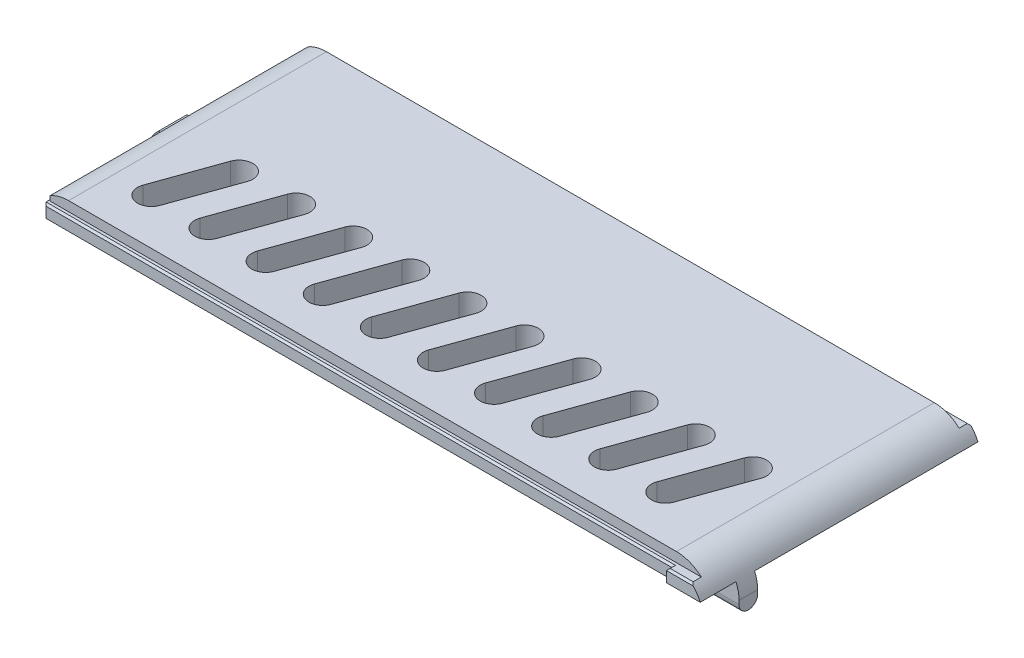
SolidWorks part; units mm, degrees
ref_plane "前视基准面" through (0, 0, 0) normal (0, 0, 1) x (1, 0, 0)
ref_plane "上视基准面" through (0, 0, 0) normal (0, 1, 0) x (1, 0, 0)
ref_plane "右视基准面" through (0, 0, 0) normal (1, 0, 0) x (0, 0, -1)
sketch "草图2" plane through (0, 0, 0) normal (0, 1, 0) x (1, 0, 0)
  line L1 (-31.0872, 15.1404) -> (42.9128, 15.1404)
  line L2 (-31.0872, 15.1404) -> (-31.0872, -12.8596)
  line L3 (-31.0872, -12.8596) -> (42.9128, -12.8596)
  line L4 (42.9128, 15.1404) -> (42.9128, -12.8596)
  dimension "D1" = 74
  dimension "D2" = 28
extrude "凸台-拉伸1" add sketch "草图2" along normal blind 4
fillet "圆角1" radius 4 2 edges at (-31.0872, 4, -1.1404) (42.9128, 4, -1.1404)
sketch "草图3" plane through (0, 0, -15.1404) normal (0, 0, -1) x (-1, 0, 0)
  line L1 (31.0872, 0) -> (-42.9128, 0)
  line L2 (31.0872, 0) -> (31.0872, 1.6)
  line L3 (31.0872, 1.6) -> (-42.9128, 1.6)
  line L4 (-42.9128, 0) -> (-42.9128, 1.6)
  point P4 (0, 0)
  point P5 (0, 0)
  point P6 (0, 0)
  point P9 (31.0872, 0)
  dimension "D1" = 1.6
extrude "切除-拉伸1" cut sketch "草图3" against normal through all
sketch "草图15" plane through (0, 1.6, 0) normal (0, -1, 0) x (1, 0, 0)
  line L1 (45.2778, 8.0374) -> (33.5789, 8.0374)
  line L2 (45.2778, 8.0374) -> (45.2778, 10.0596)
  line L3 (45.2778, 10.0596) -> (33.5789, 10.0596)
  line L4 (33.5789, 8.0374) -> (33.5789, 10.0596)
  line L5 (42.5789, -15.1404) -> (42.5789, 12.8596) construction
  dimension "D1" = 2.0222
  dimension "D2" = 9
extrude "凸台-拉伸8" add sketch "草图15" along normal blind 3
sketch "草图17" plane through (0, 0, 10.0596) normal (0, 0, 1) x (1, 0, 0)
  line L0 (42.9128, 0) -> (42.9128, -28) construction
  line L1 (42.9128, 0) -> (42.9128, -1.4)
  line L2 (45.2778, -1.4) -> (33.5789, -1.4) construction
  line L3 (42.9128, -1.4) -> (46.903, -1.4)
  line L4 (46.903, -1.4) -> (46.903, 1.6)
  line L5 (46.903, 1.6) -> (42.5789, 1.6)
  arc A0 (42.5789, 1.6) -> (42.9128, 0) centre (38.9128, 0) cw
extrude "切除-拉伸5" cut sketch "草图17" against normal through all
chamfer "倒角3" distance 3.5 angle 19 1 edges at (33.5789, 0.1, 10.0596) first distance on face at (39.129, 0.0834, 10.0596)
sketch "草图4" plane through (0, 0, 12.8596) normal (0, 0, 1) x (1, 0, 0)
  line L0 (-31.0872, 0) -> (-31.0872, -28) construction
  line L1 (-31.0872, -1.1213) -> (-29.0872, -1.1213)
  line L2 (-31.0872, -1.1213) -> (-31.0872, 6.7558)
  line L3 (-31.0872, 6.7558) -> (-29.0872, 6.7558)
  line L4 (-29.0872, -1.1213) -> (-29.0872, 6.7558)
  dimension "D1" = 2
extrude "切除-拉伸2" cut sketch "草图4" against normal through all
sketch "草图5" plane through (0, 0, 12.8596) normal (0, 0, 1) x (1, 0, 0)
  line L0 (-29.0872, 1.6) -> (42.5789, 1.6) construction
  line L1 (38.9128, 1.6) -> (-29.0872, 1.6)
  line L2 (38.9128, 1.6) -> (38.9128, 2.95)
  line L3 (38.9128, 2.95) -> (-29.0872, 2.95)
  line L4 (-29.0872, 1.6) -> (-29.0872, 2.95)
  line L6 (-29.0872, 1.6) -> (-29.0872, 3.4641) construction
  dimension "D1" = 1.35
extrude "凸台-拉伸2" add sketch "草图5" along normal blind 0.5
sketch "草图6" plane through (0, 0, -15.1404) normal (0, 0, -1) x (-1, 0, 0)
  line L4 (-38.9128, 2.95) -> (-38.9128, 1.6)
  line L5 (29.0872, 2.95) -> (-38.9128, 2.95)
  line L6 (29.0872, 1.6) -> (29.0872, 2.95)
  line L7 (-38.9128, 1.6) -> (29.0872, 1.6)
  line L8 (-38.9128, 2.95) -> (-38.9128, 1.6)
  line L9 (29.0872, 2.95) -> (-38.9128, 2.95)
  line L10 (29.0872, 1.6) -> (29.0872, 2.95)
  line L11 (-38.9128, 1.6) -> (29.0872, 1.6)
  dimension "D1" = 0
extrude "凸台-拉伸3" add sketch "草图6" along normal blind 0.5
sketch "草图7" plane through (-29.0872, 0, 0) normal (-1, 0, 0) x (0, 0, 1)
  line L1 (13.3596, 2.95) -> (-15.6404, 2.95)
  line L2 (13.3596, 2.95) -> (13.3596, 1.6)
  line L3 (13.3596, 1.6) -> (-15.6404, 1.6)
  line L4 (-15.6404, 2.95) -> (-15.6404, 1.6)
extrude "凸台-拉伸4" add sketch "草图7" along normal blind 0.15
sketch "草图10" plane through (0, 0, -15.1404) normal (0, 0, -1) x (-1, 0, 0)
  line L0 (-38.9128, 2.95) -> (-42.3685, 2.95) construction
  line L1 (-42.5789, 1.6) -> (-38.9128, 1.6)
  line L2 (-38.9128, 1.6) -> (-38.9128, 2.95)
  line L3 (-38.9128, 2.95) -> (-41.6142, 2.95)
  arc A0 (-42.5789, 1.6) -> (-41.6142, 2.95) centre (-38.9128, 0) cw
extrude "凸台-拉伸5" add sketch "草图10" along normal blind 1.08
sketch "草图11" plane through (0, 0, 12.8596) normal (0, 0, 1) x (1, 0, 0)
  line L3 (38.9128, 1.6) -> (42.5789, 1.6)
  line L4 (38.9128, 2.95) -> (38.9128, 1.6)
  line L5 (41.6142, 2.95) -> (38.9128, 2.95)
  line L6 (38.9128, 1.6) -> (42.5789, 1.6)
  line L7 (38.9128, 2.95) -> (38.9128, 1.6)
  line L8 (41.6142, 2.95) -> (38.9128, 2.95)
  arc A1 (42.5789, 1.6) -> (41.6142, 2.95) centre (38.9128, 0) ccw
  arc A2 (42.5789, 1.6) -> (41.6142, 2.95) centre (38.9128, 0) ccw
  dimension "D1" = 0
extrude "凸台-拉伸6" add sketch "草图11" along normal blind 1.08
chamfer "倒角1" distance 0.2 angle 45 9 edges at (40.2635, 2.95, -16.2204) (40.2635, 2.95, 13.9396) (4.8378, 2.95, -15.6404) (-29.2372, 2.275, -15.6404) (-29.2372, 1.6, -1.1404) (-29.2372, 2.275, 13.3596) (4.8378, 2.95, 13.3596) (38.9128, 2.95, -15.9304) (38.9128, 2.95, 13.6496)
sketch "草图12" plane through (-29.2372, 0, 0) normal (-1, 0, 0) x (0, 0, 1)
  line L0 (-1.1404, 1.8) -> (-1.1404, 4.7248) construction
  line L2 (-15.4404, 1.8) -> (13.1596, 1.8) construction
  line L3 (14.3032, 2.375) -> (12.788, 2.375) construction
  line L4 (13.1596, 1.8) -> (13.1596, 2.95) construction
  line L6 (0.4096, 2.95) -> (-2.6904, 2.95)
  line L7 (0.4096, 2.95) -> (0.4096, 1.8)
  line L8 (0.4096, 1.8) -> (-2.6904, 1.8)
  line L9 (-2.6904, 2.95) -> (-2.6904, 1.8)
  line L10 (0.4096, 2.95) -> (-2.6904, 1.8) construction
  line L11 (0.4096, 1.8) -> (-2.6904, 2.95) construction
  point P3 (-1.1404, 1.8)
  point P6 (-1.1404, 2.375)
  point P9 (13.1596, 2.375)
  dimension "D1" = 3.1
extrude "凸台-拉伸7" add sketch "草图12" along normal blind 10
sketch "草图14" plane through (0, 0, -2.6904) normal (0, 0, -1) x (-1, 0, 0)
  line L0 (39.2372, 1.8) -> (29.2372, 1.8) construction
  line L1 (39.2372, 2.95) -> (29.2372, 2.95) construction
  line L2 (29.7886, 2.95) -> (40.0135, 2.95)
  line L3 (40.0135, 2.95) -> (40.0135, 1.8)
  line L4 (40.0135, 1.8) -> (30.6593, 1.8)
  arc A0 (30.6593, 1.8) -> (29.7886, 2.95) centre (27.0872, 0) ccw
  arc A1 (31.0872, 0) -> (27.0872, 4) centre (27.0872, 0) ccw construction
extrude "切除-拉伸3" cut sketch "草图14" against normal through all
fillet "圆角2" radius 1 2 edges at (38.2459, -1.4, 8.0374) (39.9959, -1.4, 10.0596)
sketch "草图19" plane through (0, 4, 0) normal (0, 1, 0) x (1, 0, 0)
  line L0 (-20.5872, -0.8596) -> (-23.0872, -7.8596) construction
  line L5 (-19.1746, -1.3641) -> (-21.6746, -8.3641)
  line L8 (-21.9998, -0.3551) -> (-24.4998, -7.3551)
  line L11 (38.9128, 15.1404) -> (-27.0872, 15.1404) construction
  line L14 (-27.0872, -12.8596) -> (38.9128, -12.8596) construction
  line L17 (-14.3872, -0.8596) -> (-16.8872, -7.8596) construction
  line L20 (-12.9746, -1.3641) -> (-15.4746, -8.3641)
  line L23 (-15.7998, -0.3551) -> (-18.2998, -7.3551)
  line L26 (-40.9597, 1.1404) -> (-18.0872, 1.1404) construction
  line L27 (-27.0872, 15.1404) -> (-27.0872, -12.8596) construction
  line L28 (-8.1872, -0.8596) -> (-10.6872, -7.8596) construction
  line L31 (-6.7746, -1.3641) -> (-9.2746, -8.3641)
  line L34 (-9.5998, -0.3551) -> (-12.0998, -7.3551)
  line L37 (-1.9872, -0.8596) -> (-4.4872, -7.8596) construction
  line L40 (-0.5746, -1.3641) -> (-3.0746, -8.3641)
  line L43 (-3.3998, -0.3551) -> (-5.8998, -7.3551)
  line L46 (4.2128, -0.8596) -> (1.7128, -7.8596) construction
  line L49 (5.6254, -1.3641) -> (3.1254, -8.3641)
  line L52 (2.8002, -0.3551) -> (0.3002, -7.3551)
  line L53 (10.4128, -0.8596) -> (7.9128, -7.8596) construction
  line L54 (11.8254, -1.3641) -> (9.3254, -8.3641)
  line L55 (9.0002, -0.3551) -> (6.5002, -7.3551)
  line L56 (16.6128, -0.8596) -> (14.1128, -7.8596) construction
  line L57 (18.0254, -1.3641) -> (15.5254, -8.3641)
  line L58 (15.2002, -0.3551) -> (12.7002, -7.3551)
  line L59 (22.8128, -0.8596) -> (20.3128, -7.8596) construction
  line L60 (24.2254, -1.3641) -> (21.7254, -8.3641)
  line L61 (21.4002, -0.3551) -> (18.9002, -7.3551)
  line L62 (29.0128, -0.8596) -> (26.5128, -7.8596) construction
  line L63 (30.4254, -1.3641) -> (27.9254, -8.3641)
  line L64 (27.6002, -0.3551) -> (25.1002, -7.3551)
  line L65 (35.2128, -0.8596) -> (32.7128, -7.8596) construction
  line L66 (36.6254, -1.3641) -> (34.1254, -8.3641)
  line L67 (33.8002, -0.3551) -> (31.3002, -7.3551)
  arc A32 (-19.1746, -1.3641) -> (-21.9998, -0.3551) centre (-20.5872, -0.8596) ccw
  arc A33 (-24.4998, -7.3551) -> (-21.6746, -8.3641) centre (-23.0872, -7.8596) ccw
  arc A34 (-12.9746, -1.3641) -> (-15.7998, -0.3551) centre (-14.3872, -0.8596) ccw
  arc A35 (-18.2998, -7.3551) -> (-15.4746, -8.3641) centre (-16.8872, -7.8596) ccw
  arc A36 (-6.7746, -1.3641) -> (-9.5998, -0.3551) centre (-8.1872, -0.8596) ccw
  arc A37 (-12.0998, -7.3551) -> (-9.2746, -8.3641) centre (-10.6872, -7.8596) ccw
  arc A38 (-0.5746, -1.3641) -> (-3.3998, -0.3551) centre (-1.9872, -0.8596) ccw
  arc A39 (-5.8998, -7.3551) -> (-3.0746, -8.3641) centre (-4.4872, -7.8596) ccw
  arc A40 (5.6254, -1.3641) -> (2.8002, -0.3551) centre (4.2128, -0.8596) ccw
  arc A41 (0.3002, -7.3551) -> (3.1254, -8.3641) centre (1.7128, -7.8596) ccw
  arc A42 (11.8254, -1.3641) -> (9.0002, -0.3551) centre (10.4128, -0.8596) ccw
  arc A43 (6.5002, -7.3551) -> (9.3254, -8.3641) centre (7.9128, -7.8596) ccw
  arc A44 (18.0254, -1.3641) -> (15.2002, -0.3551) centre (16.6128, -0.8596) ccw
  arc A45 (12.7002, -7.3551) -> (15.5254, -8.3641) centre (14.1128, -7.8596) ccw
  arc A46 (24.2254, -1.3641) -> (21.4002, -0.3551) centre (22.8128, -0.8596) ccw
  arc A47 (18.9002, -7.3551) -> (21.7254, -8.3641) centre (20.3128, -7.8596) ccw
  arc A48 (30.4254, -1.3641) -> (27.6002, -0.3551) centre (29.0128, -0.8596) ccw
  arc A49 (25.1002, -7.3551) -> (27.9254, -8.3641) centre (26.5128, -7.8596) ccw
  arc A50 (36.6254, -1.3641) -> (33.8002, -0.3551) centre (35.2128, -0.8596) ccw
  arc A51 (31.3002, -7.3551) -> (34.1254, -8.3641) centre (32.7128, -7.8596) ccw
  point P2 (-21.8372, -4.3596)
  point P15 (-15.6372, -4.3596)
  point P22 (-9.4372, -4.3596)
  point P29 (-3.2372, -4.3596)
  point P36 (2.9628, -4.3596)
  point P43 (9.1628, -4.3596)
  point P50 (15.3628, -4.3596)
  point P57 (21.5628, -4.3596)
  point P64 (-27.0872, 1.1404)
  point P68 (27.7628, -4.3596)
  point P75 (33.9628, -4.3596)
  dimension "D6" = 4
  dimension "D3" = 1.5
  dimension "D1" = 16
  dimension "D2" = 5
  dimension "D4" = 6.5
  dimension "D5" = 10
extrude "切除-拉伸6" cut sketch "草图19" against normal up to next
